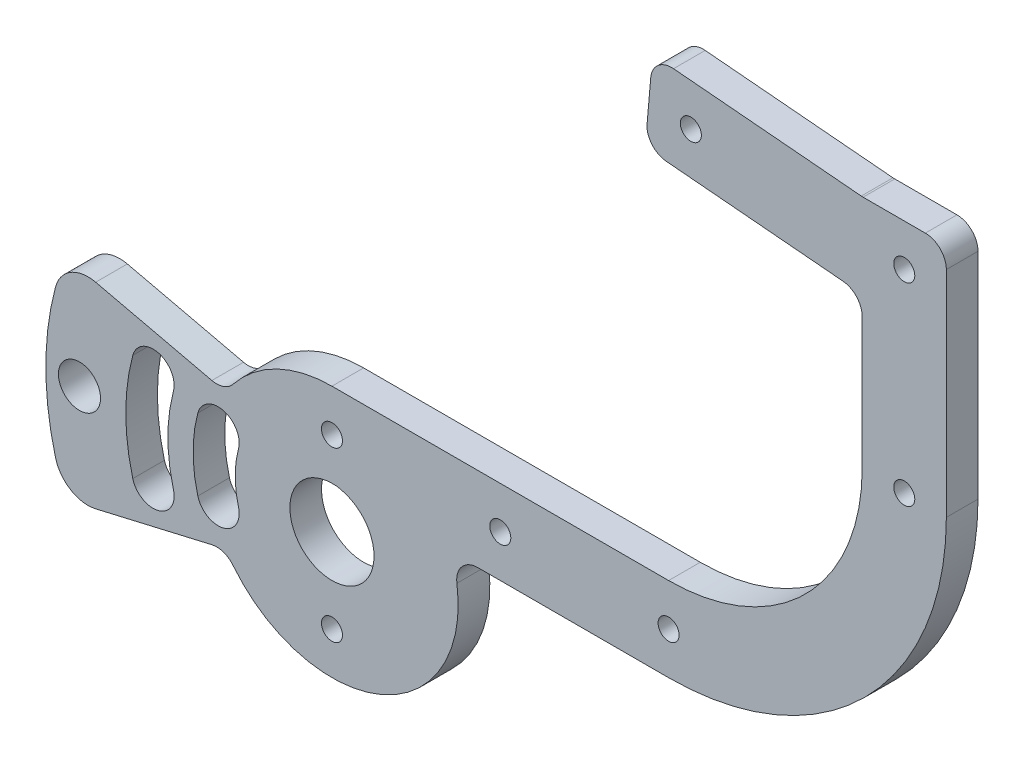
SolidWorks part; units mm, degrees
material "1060 Alloy"
ref_plane "Front Plane" through (0, 0, 0) normal (0, 0, 1) x (1, 0, 0)
ref_plane "Top Plane" through (0, 0, 0) normal (0, 1, 0) x (1, 0, 0)
ref_plane "Right Plane" through (0, 0, 0) normal (1, 0, 0) x (0, 0, -1)
sketch "Sketch1" plane through (0, 0, 0) normal (0, 0, 1) x (1, 0, 0)
  line L0 (0, 19.05) -> (50.8, 19.05)
  line L1 (50.8, 48.26) -> (92.71, 48.26) construction
  line L2 (0, 6.35) -> (50.8, 6.35)
  line L3 (0, 0) -> (-38.1, 0) construction
  line L4 (0, -5.08) -> (-38.1, -5.08)
  line L5 (0, 5.08) -> (-38.1, 5.08)
  line L6 (-36.8018, 9.861) -> (0, 0) construction
  line L7 (-35.6513, 14.809) -> (1.4381, 6.185)
  line L8 (0, 0) -> (-17.1742, 4.6018) construction
  line L9 (-17.1742, 4.6018) -> (-26.988, 7.2314) construction
  line L10 (-26.988, 7.2314) -> (-36.8018, 9.861) construction
  line L11 (-38.1, 0) -> (0, 0)
  line L12 (-35.6513, -14.809) -> (1.4381, -6.185)
  line L13 (50.8, 48.26) -> (50.8, 6.35) construction
  line L14 (80.01, 48.26) -> (80.01, 71.0715)
  line L15 (92.71, 48.26) -> (92.71, 83.82)
  line L16 (92.71, 83.82) -> (80.01, 83.82)
  line L17 (80.01, 83.82) -> (48.3808, 86.5872)
  line L18 (48.3808, 86.5872) -> (47.2739, 73.9355)
  line L19 (47.2739, 73.9355) -> (80.01, 71.0715)
  circle A0 centre (0, 0) radius 19.05
  circle A1 centre (0, 0) radius 6.35
  arc A2 (0, -5.08) -> (0, 5.08) centre (0, 0) ccw
  arc A3 (-38.1, 5.08) -> (-38.1, -5.08) centre (-38.1, 0) ccw
  circle A4 centre (-38.1, 0) radius 3.175
  arc A7 (-38.1, 0) -> (-36.8018, 9.861) centre (0, 0) cw construction
  arc A8 (-41.7087, 11.1758) -> (-43.18, 0) centre (0, 0) ccw
  arc A9 (-31.8949, 8.5462) -> (-33.02, 0) centre (0, 0) ccw
  arc A10 (-31.8949, 8.5462) -> (-41.7087, 11.1758) centre (-36.8018, 9.861) ccw
  arc A11 (-43.18, 0) -> (-33.02, 0) centre (-38.1, 0) ccw
  arc A12 (-17.78, 0) -> (-17.1742, 4.6018) centre (0, 0) cw construction
  arc A13 (-20.241, 5.4236) -> (-20.955, 0) centre (0, 0) ccw
  arc A14 (-14.1073, 3.7801) -> (-14.605, 0) centre (0, 0) ccw
  arc A15 (-14.1073, 3.7801) -> (-20.241, 5.4236) centre (-17.1742, 4.6018) ccw
  arc A16 (-20.955, 0) -> (-14.605, 0) centre (-17.78, 0) ccw
  arc A17 (-27.94, 0) -> (-26.988, 7.2314) centre (0, 0) cw construction
  arc A18 (-30.0548, 8.0532) -> (-31.115, 0) centre (0, 0) ccw
  arc A19 (-23.9212, 6.4097) -> (-24.765, 0) centre (0, 0) ccw
  arc A20 (-23.9212, 6.4097) -> (-30.0548, 8.0532) centre (-26.988, 7.2314) ccw
  arc A21 (-31.115, 0) -> (-24.765, 0) centre (-27.94, 0) ccw
  arc A22 (-17.78, 0) -> (-17.1742, -4.6018) centre (0, 0) ccw construction
  arc A23 (-20.241, -5.4236) -> (-20.955, 0) centre (0, 0) cw
  arc A24 (-14.1073, -3.7801) -> (-14.605, 0) centre (0, 0) cw
  arc A25 (-14.1073, -3.7801) -> (-20.241, -5.4236) centre (-17.1742, -4.6018) cw
  arc A26 (-20.955, 0) -> (-14.605, 0) centre (-17.78, 0) cw
  arc A27 (-27.94, 0) -> (-26.988, -7.2314) centre (0, 0) ccw construction
  arc A28 (-30.0548, -8.0532) -> (-31.115, 0) centre (0, 0) cw
  arc A29 (-23.9212, -6.4097) -> (-24.765, 0) centre (0, 0) cw
  arc A30 (-23.9212, -6.4097) -> (-30.0548, -8.0532) centre (-26.988, -7.2314) cw
  arc A31 (-31.115, 0) -> (-24.765, 0) centre (-27.94, 0) cw
  arc A32 (-38.1, 0) -> (-36.8018, -9.861) centre (0, 0) ccw construction
  arc A33 (-41.7087, -11.1758) -> (-43.18, 0) centre (0, 0) cw
  arc A34 (-31.8949, -8.5462) -> (-33.02, 0) centre (0, 0) cw
  arc A35 (-31.8949, -8.5462) -> (-41.7087, -11.1758) centre (-36.8018, -9.861) cw
  arc A36 (-43.18, 0) -> (-33.02, 0) centre (-38.1, 0) cw
  arc A37 (50.8, 6.35) -> (92.71, 48.26) centre (50.8, 48.26) ccw
  arc A38 (50.8, 19.05) -> (80.01, 48.26) centre (50.8, 48.26) ccw
  point P8 (-19.05, 0)
  point P18 (-17.6279, 2.3208)
  point P22 (-37.774, 4.973)
  point P37 (-27.701, 3.6469)
  point P50 (-17.6279, -2.3208)
  point P57 (-27.701, -3.6469)
  point P63 (-37.774, -4.973)
  dimension "D1" = 12.7
  dimension "D4" = 5.08
  dimension "D8" = 6.35
  dimension "D6" = 27.94
  dimension "D7" = 17.78
  dimension "D2" = 12.7
  dimension "D3" = 50.8
  dimension "D5" = 38.1
  dimension "D9" = 15
  dimension "D10" = 50.8
  dimension "D11" = 90
  dimension "D12" = 41.91
  dimension "D13" = 35.56
  dimension "D14" = 12.7
  dimension "D15" = 12.7
  dimension "D16" = 31.75
  dimension "D17" = 95
extrude "Boss-Extrude1" add sketch "Sketch1" along normal blind 4.7752 contours L2 A0 L7 | A0 L2 L0 | A1 L12 A0 L2 L7 | A15 A14 L5 A1 L2 L7 A0 | A24 A25 A0 L12 A1 L4 | A24 L4 A1 L11 | L5 A14 L11 A1 | A20 A19 L5 A13 A15 A0 L7 A10 A9 A18 | A10 A8 A3 L5 A9 | A35 A34 L4 A3 A33 | L5 A36 A9 | A18 L5 A9 L11 | L4 A34 A11 | A34 L4 A28 L11 | L5 A19 L11 A13 | A29 L4 A23 L11 | A34 A35 L12 A0 A25 A23 L4 A29 A30 A28 | A36 A3 A11 A4 region at (25.4, 17.8239, 0) region at (1.3885, 12.1027, 0) region at (5.234, -7.6206, 0) region at (-16.9634, 9.1395, 0) region at (-9.9326, 7.123, 0) region at (-37.3508, 9.2274, 0) region at (-9.9281, -7.1226, 0) region at (-25.903, -12.3177, 0) region at (-9.9325, 2.6195, 0) region at (-37.3508, -9.2274, 0) region at (-34.0206, 3.931, 0) region at (-31.9323, 2.5454, 0) region at (-41.5905, 3.4905, 0) region at (-22.6678, 2.5508, 0) region at (-9.9325, -2.6195, 0) region at (-34.0206, -3.931, 0) region at (-31.9323, -2.5454, 0) region at (-22.6678, -2.5508, 0)
fillet "Fillet1" radius 3.175 8 edges at (17.9605, 6.35, 2.3876) (-16.0557, -10.2527, 2.3876) (-16.0557, 10.2527, 2.3876) (92.71, 83.82, 2.3876) (80.01, 71.0715, 2.3876) (47.2739, 73.9355, 2.3876) (48.3808, 86.5872, 2.3876) (80.01, 83.82, 2.3876)
sketch "Sketch2" plane through (0, 0, 4.7752) normal (0, 0, 1) x (1, 0, 0)
  line L0 (0, 12.7) -> (0, 0) construction
  line L1 (0, 0) -> (0, -12.7) construction
  line L2 (-38.1, 0) -> (0, 0) construction
  line L3 (0, 12.7) -> (25.4, 12.7) construction
  line L4 (86.36, 83.82) -> (86.36, 77.47) construction
  line L5 (80.01, 48.26) -> (86.36, 48.26) construction
  line L6 (86.36, 77.47) -> (92.71, 77.47) construction
  line L7 (92.71, 48.26) -> (92.71, 80.645) construction
  line L8 (86.36, 77.47) -> (80.01, 77.47) construction
  line L10 (25.4, 12.7) -> (50.8, 12.7) construction
  line L11 (89.535, 83.82) -> (80.1486, 83.82) construction
  line L12 (80.01, 48.26) -> (80.01, 68.1621) construction
  line L13 (47.8274, 80.2614) -> (54.1532, 79.7079) construction
  line L14 (48.1041, 83.4243) -> (47.5507, 77.0984) construction
  line L15 (54.1532, 79.7079) -> (54.7067, 86.0338) construction
  line L16 (79.8719, 83.8321) -> (51.5437, 86.3105) construction
  line L17 (54.1532, 79.7079) -> (53.5998, 73.3821) construction
  line L18 (50.4369, 73.6588) -> (77.1117, 71.3251) construction
  circle A0 centre (0, 12.7) radius 1.5875
  circle A1 centre (0, -12.7) radius 1.5875
  circle A2 centre (25.4, 12.7) radius 1.5875
  circle A6 centre (54.1532, 79.7079) radius 1.5875
  circle A7 centre (-38.1, 0) radius 3.175 construction
  circle A8 centre (50.8, 12.7) radius 1.5875
  circle A10 centre (86.36, 77.47) radius 1.5875
  circle A11 centre (86.36, 48.26) radius 1.5875
  point P38 (0, 0)
  point P40 (0, 0)
  dimension "D2" = 3.175
  dimension "D1" = 12.7
  dimension "D3" = 25.4
  dimension "D4" = 6.35
extrude "Cut-Extrude2" cut sketch "Sketch2" against normal blind 12.6492
